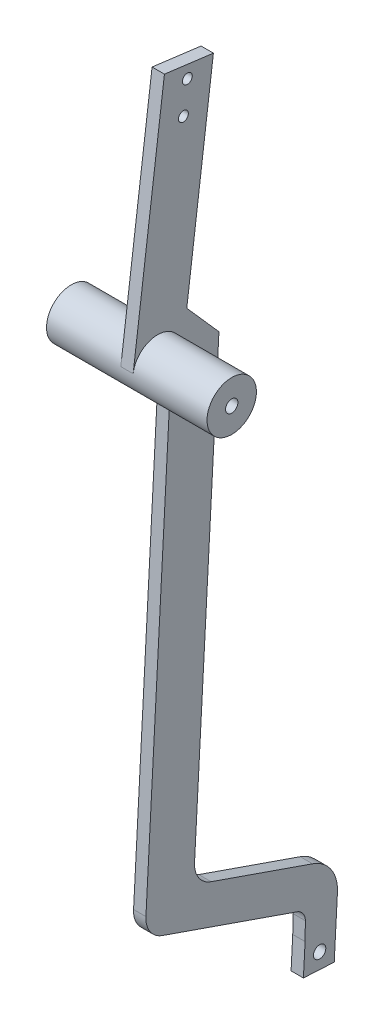
SolidWorks part; units mm, degrees
ref_plane "Front Plane" through (0, 0, 0) normal (0, 0, 1) x (1, 0, 0)
ref_plane "Top Plane" through (0, 0, 0) normal (0, 1, 0) x (1, 0, 0)
ref_plane "Right Plane" through (0, 0, 0) normal (1, 0, 0) x (0, 0, -1)
ref_plane "Plane1" through (-60.9936, 927.3025, 511.5244) normal (1, 0, 0) x (0, -0.9985, 0.0545)
sketch "Sketch3" plane through (-60.9936, 927.3025, 511.5244) normal (1, 0, 0) x (0, -0.9985, 0.0545)
  circle A0 centre (-394.0453, 76.3488) radius 20
  circle A1 centre (-394.0453, 76.3488) radius 5
  dimension "D1" = 40
extrude "Boss-Extrude1" add sketch "Sketch3" along normal mid plane 130
sketch "Sketch5" plane through (-60.9936, 927.3025, 511.5244) normal (1, 0, 0) x (0, -0.9985, 0.0545)
  line L0 (-392.5842, 96.2954) -> (-591.1232, 110.8378)
  line L1 (-594.0453, 40) -> (-594.0453, 153.138) construction
  line L2 (-395.5063, 56.4022) -> (-594.0453, 70.9447)
  line L3 (-594.0453, 70.9447) -> (-591.1232, 110.8378)
  line L5 (-592.5842, 90.8913) -> (-530.6321, 86.3534) construction
  arc A0 (-392.5842, 96.2954) -> (-395.5063, 56.4022) centre (-394.0453, 76.3488) ccw
  circle A1 centre (-394.0453, 76.3488) radius 20 construction
  circle A2 centre (-582.611, 90.1608) radius 4
  circle A3 centre (-557.6778, 88.3345) radius 4
  point P17 (-592.5842, 70.9447)
  point P18 (0, 0)
  point P19 (0, 0)
  dimension "D2" = 8
  dimension "D3" = 8
  dimension "D1" = 40
  dimension "D4" = 10
  dimension "25" = 25
extrude "Boss-Extrude2" add sketch "Sketch5" along normal mid plane 10
sketch "Sketch6" plane through (-60.9936, 927.3025, 511.5244) normal (1, 0, 0) x (0, -0.9985, 0.0545)
  line L0 (6.218, 39.6467) -> (6.218, 202.9451) construction
  line L1 (-377.6198, 87.7595) -> (-10.7016, 87.7595)
  line L2 (-394.0453, 126.0872) -> (-30.9061, 126.0872)
  line L3 (76.5403, 22.8774) -> (76.5403, 371.7765) construction
  line L4 (64.0135, 34.6467) -> (64.0135, 315.1231) construction
  line L5 (8.5212, 102.2384) -> (40.3708, 213.1287)
  line L6 (64.1206, 220.9429) -> (89.0135, 220.9429)
  line L7 (64.0135, 245.9429) -> (89.0135, 245.9429)
  line L8 (89.0135, 220.9429) -> (89.0135, 245.9429)
  line L9 (64.1206, 220.9429) -> (89.0135, 245.9429) construction
  line L10 (64.0135, 245.9429) -> (89.0135, 220.9429) construction
  line L11 (-11.6833, 140.5661) -> (12.3449, 224.2246)
  line L12 (64.0135, 245.9429) -> (41.1791, 245.9429)
  line L13 (64.1206, 220.9429) -> (49.5817, 220.3601)
  line L14 (-394.0453, 126.0872) -> (-422.0571, 98.4542)
  line L16 (-422.0571, 98.4542) -> (-387.3077, 95.1798)
  line L17 (-392.5842, 96.2954) -> (-591.1232, 110.8378) construction
  circle A0 centre (76.5403, 233.4161) radius 5
  arc A1 (49.5817, 220.3601) -> (40.3708, 213.1287) centre (49.9822, 210.3681) ccw
  arc A2 (12.3449, 224.2246) -> (41.1791, 245.9429) centre (41.1791, 215.9429) cw
  arc A3 (-30.9061, 126.0872) -> (-11.6833, 140.5661) centre (-30.9061, 146.0872) ccw
  arc A4 (-10.7016, 87.7595) -> (8.5212, 102.2384) centre (-10.7016, 107.7595) ccw
  circle A5 centre (-394.0453, 76.3488) radius 20 construction
  arc A7 (-377.6198, 87.7595) -> (-387.3077, 95.1798) centre (-394.0453, 76.3488) ccw
  point P0 (-421.4034, 107.3788)
  dimension "D1" = 10
  dimension "D5" = 10
  dimension "D6" = 30
  dimension "D7" = 20
  dimension "D8" = 20
  dimension "D2" = 25
  dimension "D3" = 25
  dimension "D4" = 30
extrude "Boss-Extrude3" add sketch "Sketch6" along normal mid plane 10
ref_plane "Plane2" through (0, 0, 395) normal (0, 0, -1) x (-1, 0, 0)
